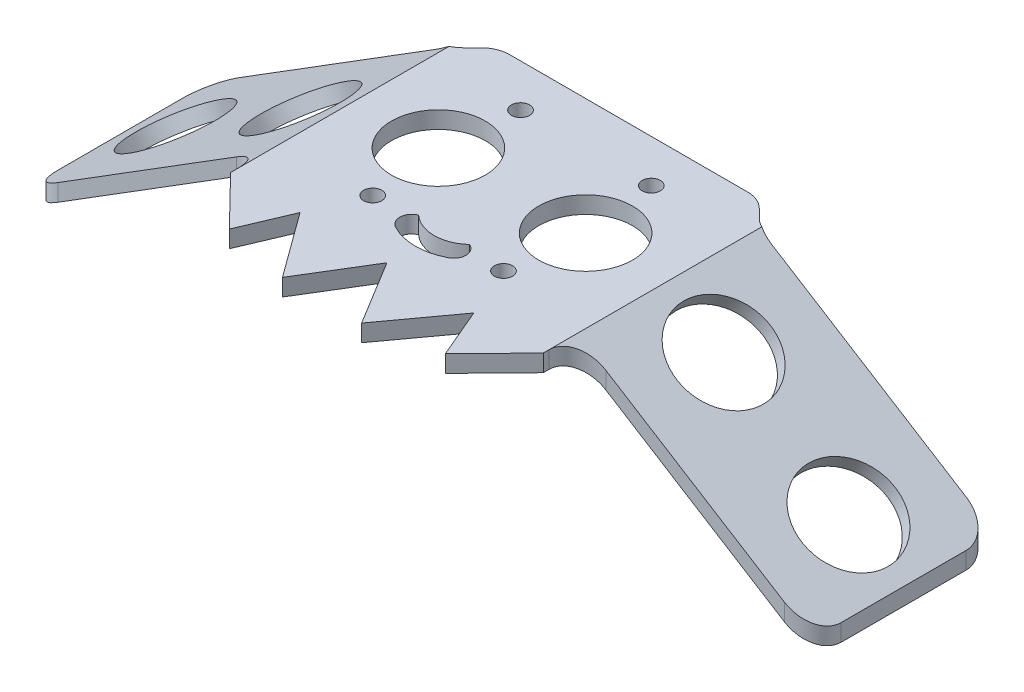
SolidWorks part; units mm, degrees
ref_plane "前视基准面" through (0, 0, 0) normal (0, 0, 1) x (1, 0, 0)
ref_plane "上视基准面" through (0, 0, 0) normal (0, 1, 0) x (1, 0, 0)
ref_plane "右视基准面" through (0, 0, 0) normal (1, 0, 0) x (0, 0, -1)
sketch "草图1" plane through (0, 0, 0) normal (0, 0, 1) x (1, 0, 0)
  line L0 (0, 148.5) -> (0, -94.9538) construction
  line L1 (105, -148.5) -> (-105, -148.5) construction
  line L2 (105, -148.5) -> (105, 148.5) construction
  line L3 (105, 148.5) -> (-105, 148.5) construction
  line L4 (-105, -148.5) -> (-105, 148.5) construction
  line L5 (105, -148.5) -> (-105, 148.5) construction
  line L6 (105, 148.5) -> (-105, -148.5) construction
  line L7 (35.8892, 121.6645) -> (-35.8892, 121.6645)
  line L8 (-35.8892, 121.6645) -> (-66.9017, 102.292)
  line L9 (-75, 40.9339) -> (-75, 31.2613)
  line L10 (-66.9017, 102.292) -> (-66.9017, 52.8701)
  line L11 (75, 40.9339) -> (75, 31.2613)
  line L12 (66.9017, 102.292) -> (66.9017, 52.8701)
  line L13 (35.8892, 121.6645) -> (66.9017, 102.292)
  line L14 (-75, 31.2613) -> (75, 31.2613)
  line L15 (-60, -148.5) -> (-60, -91.8129)
  line L16 (-75, 23.94) -> (75, 23.94)
  line L17 (-75, 23.94) -> (-75, 10.5626)
  line L18 (-38.8455, -105.5906) -> (-66.4608, -113.7617)
  line L19 (-66.4608, -113.7617) -> (-70.1743, -102.7328)
  line L20 (75, 23.94) -> (75, 10.5626)
  line L21 (66.4608, -113.7617) -> (70.1743, -102.7328)
  line L22 (38.8455, -105.5906) -> (66.4608, -113.7617)
  line L23 (-105, 93.0519) -> (105, 93.0519)
  line L24 (-105, 63.0519) -> (105, 63.0519)
  line L25 (-105, -90.0629) -> (-70.5337, -90.0629)
  line L26 (-105, -60.0629) -> (-67.4027, -60.0629)
  line L27 (60, -148.5) -> (60, 148.5)
  line L28 (-60, -58.3129) -> (-45, -58.3129)
  line L29 (-60, -61.8129) -> (-45, -61.8129)
  line L30 (-36, -58.3129) -> (-21, -58.3129)
  line L31 (-36, -61.8129) -> (-21, -61.8129)
  line L32 (-60, -88.3129) -> (-45, -88.3129)
  line L33 (-60, -91.8129) -> (-45, -91.8129)
  line L34 (-36, -88.3129) -> (-21, -88.3129)
  line L35 (-36, -91.8129) -> (-21, -91.8129)
  line L36 (-60, -58.3129) -> (-60, 148.5)
  line L37 (-19.25, -90.0629) -> (105, -90.0629)
  line L38 (-19.25, -60.0629) -> (19.25, -60.0629)
  line L39 (-60, -88.3129) -> (-60, -61.8129)
  line L40 (21, -58.3129) -> (36, -58.3129)
  line L41 (45, -58.3129) -> (60, -58.3129)
  line L42 (60, -61.8129) -> (45, -61.8129)
  line L43 (36, -61.8129) -> (21, -61.8129)
  line L44 (21, -88.3129) -> (36, -88.3129)
  line L45 (21, -91.8129) -> (36, -91.8129)
  line L46 (45, -88.3129) -> (60, -88.3129)
  line L47 (45, -91.8129) -> (60, -91.8129)
  line L48 (37.75, -60.0629) -> (43.25, -60.0629)
  line L49 (58.25, -60.0629) -> (105, -60.0629)
  line L50 (-60, 94.8019) -> (-45, 94.8019)
  line L51 (-36, 94.8019) -> (-21, 94.8019)
  line L52 (-60, 91.3019) -> (-45, 91.3019)
  line L53 (-36, 91.3019) -> (-21, 91.3019)
  line L54 (-60, 64.8019) -> (-45, 64.8019)
  line L55 (-60, 61.3019) -> (-45, 61.3019)
  line L56 (-36, 64.8019) -> (-21, 64.8019)
  line L57 (-36, 61.3019) -> (-21, 61.3019)
  line L58 (21, 94.8019) -> (36, 94.8019)
  line L59 (21, 91.3019) -> (36, 91.3019)
  line L60 (45, 94.8019) -> (60, 94.8019)
  line L61 (45, 91.3019) -> (60, 91.3019)
  line L62 (21, 61.3019) -> (36, 61.3019)
  line L63 (21, 64.8019) -> (36, 64.8019)
  line L64 (45, 61.3019) -> (60, 61.3019)
  line L65 (45, 64.8019) -> (60, 64.8019)
  line L66 (-33.1709, -104.7687) -> (33.1709, -104.7687)
  line L67 (0, -104.7687) -> (0, -148.5) construction
  arc A0 (-75, 40.9339) -> (-66.9017, 52.8701) centre (-79.7474, 52.8701) ccw
  arc A1 (75, 40.9339) -> (66.9017, 52.8701) centre (79.7474, 52.8701) cw
  arc A3 (-60, -88.3129) -> (-60, -91.8129) centre (-60, -90.0629) ccw
  arc A4 (-60, -58.3129) -> (-60, -61.8129) centre (-60, -60.0629) ccw
  circle A5 centre (-60, 63.0519) radius 1.75
  circle A6 centre (-60, 93.0519) radius 1.75
  circle A7 centre (60, 93.0519) radius 1.75
  circle A8 centre (60, 63.0519) radius 1.75
  arc A9 (60, -91.8129) -> (60, -88.3129) centre (60, -90.0629) ccw
  arc A10 (60, -61.8129) -> (60, -58.3129) centre (60, -60.0629) ccw
  arc A11 (-36, -58.3129) -> (-36, -61.8129) centre (-36, -60.0629) ccw
  arc A12 (-36, -88.3129) -> (-36, -91.8129) centre (-36, -90.0629) ccw
  arc A13 (36, -61.8129) -> (36, -58.3129) centre (36, -60.0629) ccw
  arc A14 (36, -91.8129) -> (36, -88.3129) centre (36, -90.0629) ccw
  arc A15 (-45, -61.8129) -> (-45, -58.3129) centre (-45, -60.0629) ccw
  arc A16 (-21, -61.8129) -> (-21, -58.3129) centre (-21, -60.0629) ccw
  arc A17 (-45, -91.8129) -> (-45, -88.3129) centre (-45, -90.0629) ccw
  arc A18 (-21, -91.8129) -> (-21, -88.3129) centre (-21, -90.0629) ccw
  arc A19 (45, -58.3129) -> (45, -61.8129) centre (45, -60.0629) ccw
  arc A20 (21, -58.3129) -> (21, -61.8129) centre (21, -60.0629) ccw
  arc A21 (21, -88.3129) -> (21, -91.8129) centre (21, -90.0629) ccw
  arc A22 (45, -88.3129) -> (45, -91.8129) centre (45, -90.0629) ccw
  circle A23 centre (-36, 93.0519) radius 1.75
  circle A24 centre (-36, 63.0519) radius 1.75
  circle A25 centre (36, 93.0519) radius 1.75
  circle A26 centre (36, 63.0519) radius 1.75
  circle A27 centre (-45, 93.0519) radius 1.75
  circle A28 centre (-21, 93.0519) radius 1.75
  circle A29 centre (-45, 63.0519) radius 1.75
  circle A30 centre (-21, 63.0519) radius 1.75
  circle A31 centre (21, 93.0519) radius 1.75
  circle A32 centre (21, 63.0519) radius 1.75
  circle A33 centre (45, 93.0519) radius 1.75
  circle A34 centre (45, 63.0519) radius 1.75
  arc A35 (33.1709, -104.7687) -> (38.8455, -105.5906) centre (33.1709, -124.7687) cw
  arc A36 (-33.1709, -104.7687) -> (-38.8455, -105.5906) centre (-33.1709, -124.7687) ccw
  spline S0 degree 3 poles (-75, 10.5626) (-72.6959, 1.9073) (-70.3396, -13.3728) (-67.1028, -43.6255) (-66.7657, -72.9327) (-71.8903, -95.1489) (-70.1743, -102.7328) knots 0 0 0 0 0.235247 0.406294 0.801186 1 1 1 1
  spline S1 degree 3 poles (75, 10.5626) (72.6959, 1.9073) (70.3396, -13.3728) (67.1028, -43.6255) (66.7657, -72.9327) (71.8903, -95.1489) (70.1743, -102.7328) knots 0 0 0 0 0.235247 0.406294 0.801186 1 1 1 1
  point P0 (0, 0)
  point P27 (0, 121.6645)
  point P42 (0, -94.0966)
  dimension "D1" = 60
  dimension "D4" = 20
  dimension "D5" = 24
  dimension "D7" = 24
  dimension "D9" = 15
  dimension "D10" = 15
  dimension "D13" = 24
  dimension "D17" = 15
  dimension "D2" = 30
  dimension "D3" = 30
  dimension "D6" = 24
  dimension "D8" = 24
  dimension "D11" = 15
  dimension "D12" = 15
  dimension "D14" = 24
  dimension "D15" = 24
  dimension "D16" = 24
  dimension "D18" = 15
  dimension "D19" = 15
  dimension "D20" = 15
  dimension "D21" = 15
  dimension "D22" = 15
  dimension "D23" = 15
  dimension "D24" = 15
  dimension "D25" = 15
  dimension "D26" = 15
  dimension "D27" = 15
  dimension "D28" = 15
  dimension "D29" = 3.5
  dimension "D30" = 3.5
  dimension "D31" = 3.5
extrude "凸台-拉伸1" add sketch "草图1" along normal blind 3 contours A34 L24 A26 L62 A32 A30 L57 A24 A29 L55 L36 L14 L27 L64 | A5 L24 L10 A0 L9 L14 L36 | A6 L23 L10 L24 A5 L36 | A6 L36 L8 L10 L23 | A33 L60 L27 L13 L7 L8 L36 L50 A27 L23 A23 L51 A28 A31 L58 A25 | A34 L65 L27 L61 A33 L23 A25 L59 A31 A28 L53 A23 A27 L52 L36 L54 A29 L24 A24 L56 A30 A32 L63 A26 | A7 L23 L12 L13 L27 | A8 L24 L12 L23 A7 L27 | A8 L27 L14 L11 A1 L12 L24 | A22 L46 L27 L42 A19 A13 L43 A20 A16 L31 A11 L30 L40 L41 L16 L36 L28 A15 L29 L39 L32 A17 L33 L15 L18 L22 L47 A14 L45 A21 A18 L35 A12 L34 | L17 S0 L19 L18 L15 A3 L39 A4 L36 L16 | S1 L20 L16 L27 A10 L49 | S1 L49 A10 L27 A9 L37 | S1 L37 A9 L27 L22 L21 region at (0, 106.7597, 0) region at (63.3118, 98.9762, 0) region at (-63.3118, 98.9762, 0) region at (63.5153, 78.0519, 0) region at (-63.5153, 78.0519, 0) region at (65.7633, 44.067, 0) region at (0, 78.0519, 0) region at (-65.7633, 44.067, 0) region at (0, 46.6707, 0) region at (0, -40.0712, 0) region at (65.6849, -11.6712, 0) region at (-65.3451, -38.0027, 0) region at (64.4303, -76.0355, 0) region at (65.0264, -100.7629, 0)
sketch "草图7" plane through (0, 0, 0) normal (0, 0, -1) x (-1, 0, 0)
  line L0 (0, 121.6645) -> (0, -104.7687) construction
  line L1 (-35.8892, 121.6645) -> (35.8892, 121.6645) construction
  line L2 (33.1709, -104.7687) -> (-33.1709, -104.7687) construction
  line L3 (0, 41.2613) -> (-21, 41.2613) construction
  line L4 (0, 41.2613) -> (21, 41.2613) construction
  line L5 (0, 13.94) -> (-21, 13.94) construction
  line L6 (0, 13.94) -> (21, 13.94) construction
  line L7 (75, 23.94) -> (-75, 23.94) construction
  line L8 (75, 31.2613) -> (-75, 31.2613) construction
  circle A0 centre (-21, 41.2613) radius 2.25
  circle A1 centre (21, 41.2613) radius 2.25
  circle A2 centre (-21, 13.94) radius 2.25
  circle A3 centre (21, 13.94) radius 2.25
  dimension "D1" = 10
  dimension "D2" = 10
extrude "切除-拉伸2" cut sketch "草图7" against normal through all
sketch "草图8" plane through (0, 0, 3) normal (0, 0, 1) x (1, 0, 0)
  line L0 (0, 121.6645) -> (0, -1.9696) construction
  line L1 (35.8892, 121.6645) -> (-35.8892, 121.6645) construction
  line L2 (-33.1709, -104.7687) -> (33.1709, -104.7687) construction
  line L3 (-33.409, 20.409) -> (-12.6214, -0.3786)
  line L4 (31.818, -51.182) -> (-31.818, -51.182)
  line L5 (35, -48) -> (35, 15.6418)
  line L8 (-35, 18.818) -> (-12.6214, -3.5605) construction
  line L9 (-33.409, -52.773) -> (-12.5737, -31.9377)
  line L10 (-36.591, 17.227) -> (-15.8034, -3.5605)
  line L11 (33.4105, 20.4105) -> (12.573, -0.427)
  line L12 (15.803, -3.5609) -> (36.5881, 17.2241)
  line L13 (31.8195, 18.8195) -> (-31.818, 18.818)
  line L14 (-15.8038, -28.8038) -> (-36.591, -49.591)
  line L15 (12.5534, -31.9174) -> (33.409, -52.773)
  line L16 (34.9993, 18.8173) -> (12.6207, -3.5613) construction
  line L17 (0, -30.3951) -> (0, -104.7687) construction
  line L18 (-35, -48) -> (-35, 15.636)
  line L19 (-11.9624, -1.9696) -> (-14.2124, -1.9696) construction
  line L20 (15.8034, -28.8034) -> (36.591, -49.591)
  line L21 (14.2117, -30.3951) -> (11.9607, -30.3951) construction
  line L22 (14.2117, -30.3951) -> (14.2117, -28.1441) construction
  line L23 (14.2117, -1.9696) -> (11.9612, -1.9696) construction
  line L24 (-14.2124, -30.3951) -> (-14.2124, -28.1446) construction
  line L25 (14.2117, -30.3951) -> (12.62, -28.8034) construction
  line L26 (14.2117, -1.9696) -> (12.6204, -3.5609) construction
  line L27 (12.6207, -28.8027) -> (35, -51.182) construction
  line L28 (-12.6215, -3.5606) -> (-14.2124, -1.9696) construction
  line L29 (-14.2124, -4.2196) -> (-14.2124, -1.9696) construction
  line L30 (-12.6214, -28.8034) -> (-35, -51.182) construction
  line L31 (-12.6211, -28.8037) -> (-14.2124, -30.3951) construction
  line L32 (-11.9619, -30.3951) -> (-14.2124, -30.3951) construction
  line L33 (14.2117, -4.2201) -> (14.2117, -1.9696) construction
  line L34 (11.0312, -30.3951) -> (0, -30.3951) construction
  arc A0 (-33.409, 20.409) -> (-36.591, 17.227) centre (-35, 18.818) ccw
  arc A1 (36.5881, 17.2241) -> (33.4105, 20.4105) centre (34.9993, 18.8173) ccw
  arc A2 (-36.591, -49.591) -> (-33.409, -52.773) centre (-35, -51.182) ccw
  arc A3 (33.409, -52.773) -> (36.591, -49.591) centre (35, -51.182) ccw
  arc A4 (-15.8034, -3.5605) -> (-12.6214, -0.3786) centre (-14.2124, -1.9696) ccw
  arc A5 (12.6692, -0.3308) -> (15.803, -3.5609) centre (14.2117, -1.9696) ccw
  arc A6 (-12.6699, -32.0338) -> (-15.8038, -28.8038) centre (-14.2124, -30.3951) ccw
  arc A7 (15.8034, -28.8034) -> (12.6894, -32.0534) centre (14.2117, -30.3951) ccw
  circle A8 centre (-0.0004, -16.1823) radius 8
  point P6 (0, -16.182)
  point P13 (-0.0004, -16.1823)
extrude "切除-拉伸3" cut sketch "草图8" against normal through all contours L10 A4 L3 A0 | L11 A5 L12 A1 | L20 A7 L15 A3 | L9 A6 L14 A2 | A8 region at (-24.6062, 8.4242, 3) region at (24.6054, 8.4234, 3) region at (-24.6061, -40.7881, 3) region at (24.6056, -40.7877, 3) region at (-0.0004, -16.1823, 3)
sketch "草图9" plane through (0, 0, 3) normal (0, 0, 1) x (1, 0, 0)
  line L0 (-70.7828, -98.747) -> (70.7828, -98.747) construction
  line L1 (0, -98.747) -> (0, -104.7687) construction
  line L2 (55, -100.497) -> (20, -100.497)
  line L3 (-55, -96.997) -> (-20, -96.997)
  line L4 (-55, -100.497) -> (-20, -100.497)
  line L5 (-33.1709, -104.7687) -> (33.1709, -104.7687) construction
  line L6 (55, -96.997) -> (20, -96.997)
  arc A0 (-55, -96.997) -> (-55, -100.497) centre (-55, -98.747) ccw
  arc A1 (-20, -100.497) -> (-20, -96.997) centre (-20, -98.747) ccw
  arc A2 (20, -100.497) -> (20, -96.997) centre (20, -98.747) cw
  arc A3 (55, -96.997) -> (55, -100.497) centre (55, -98.747) cw
  spline S0 degree 3 poles (-75, 10.5626) (-72.6959, 1.9073) (-70.3396, -13.3728) (-67.1028, -43.6255) (-66.7657, -72.9327) (-71.8903, -95.1489) (-70.1743, -102.7328) knots 0 0 0 0 0.235247 0.406294 0.801186 1 1 1 1 construction
  spline S1 degree 3 poles (75, 10.5626) (72.6959, 1.9073) (70.3396, -13.3728) (67.1028, -43.6255) (66.7657, -72.9327) (71.8903, -95.1489) (70.1743, -102.7328) knots 0 0 0 0 0.235247 0.406294 0.801186 1 1 1 1 construction
  dimension "D1" = 35
  dimension "D2" = 20
extrude "切除-拉伸4" cut sketch "草图9" against normal blind 3
sketch "草图10" plane through (0, 0, 3) normal (0, 0, 1) x (1, 0, 0)
  line L0 (-21, -60.0629) -> (-21, -90.0629) construction
  line L1 (21, -60.0629) -> (21, -90.0629) construction
  line L2 (-21, -75.0629) -> (-17.5, -75.0629) construction
  line L4 (12.5, -80.0629) -> (-12.5, -80.0629)
  line L6 (12.5, -70.0629) -> (-12.5, -70.0629)
  line L11 (17.5, -75.0629) -> (21, -75.0629) construction
  arc A0 (-12.5, -70.0629) -> (-12.5, -80.0629) centre (-12.5, -75.0629) ccw
  arc A1 (12.5, -80.0629) -> (12.5, -70.0629) centre (12.5, -75.0629) ccw
  point P11 (0, -75.0629)
extrude "切除-拉伸5" cut sketch "草图10" against normal blind 3
sketch "草图11" plane through (0, 0, 3) normal (0, 0, 1) x (1, 0, 0)
  line L0 (-21, 93.0519) -> (-21, 63.0519) construction
  line L1 (21, 93.0519) -> (21, 63.0519) construction
  line L2 (-21, 78.0519) -> (-20, 78.0519) construction
  line L4 (15, 73.0519) -> (-15, 73.0519)
  line L6 (15, 83.0519) -> (-15, 83.0519)
  line L10 (20, 78.0519) -> (21, 78.0519) construction
  arc A0 (-15, 83.0519) -> (-15, 73.0519) centre (-15, 78.0519) ccw
  arc A1 (15, 73.0519) -> (15, 83.0519) centre (15, 78.0519) ccw
  point P10 (0, 78.0519)
  dimension "D1" = 30
extrude "切除-拉伸8" cut sketch "草图11" against normal blind 3
sketch "草图12" plane through (0, 0, 3) normal (0, 0, 1) x (1, 0, 0)
  line L0 (0, 121.6645) -> (0, 83.0519) construction
  line L1 (35.8892, 121.6645) -> (-35.8892, 121.6645) construction
  line L2 (15, 83.0519) -> (-15, 83.0519) construction
  circle A0 centre (0, 106.3718) radius 11 construction
  circle A1 centre (0, 106.3718) radius 8 construction
  circle A2 centre (0, 114.3718) radius 1.7
  circle A3 centre (0, 98.3718) radius 1.7
  circle A4 centre (8, 106.3718) radius 1.7
  circle A5 centre (-8, 106.3718) radius 1.7
extrude "切除-拉伸9" cut sketch "草图12" against normal blind 3
sketch "草图13" plane through (0, 0, 3) normal (0, 0, 1) x (1, 0, 0)
  line L0 (0, -104.7687) -> (0, -80.0629) construction
  line L1 (-33.1709, -104.7687) -> (33.1709, -104.7687) construction
  line L2 (-12.5, -80.0629) -> (12.5, -80.0629) construction
  circle A0 centre (0, -92.4158) radius 8 construction
  circle A1 centre (0, -84.4158) radius 1.7
  circle A2 centre (8, -92.4158) radius 1.7
  circle A3 centre (0, -100.4158) radius 1.7
  circle A4 centre (-8, -92.4158) radius 1.7
extrude "切除-拉伸11" cut sketch "草图13" against normal blind 3
sketch "草图14" plane through (0, 0, 3) normal (0, 0, 1) x (1, 0, 0)
  line L0 (0, 23.94) -> (0, -104.7687) construction
  line L1 (-55.4755, 8.9197) -> (-55.4755, -46.0803)
  line L2 (-58.9755, 8.9197) -> (-58.9755, -46.0803)
  line L3 (-75, 23.94) -> (75, 23.94) construction
  line L4 (-33.1709, -104.7687) -> (33.1709, -104.7687) construction
  line L5 (58.9755, 8.9197) -> (58.9755, -46.0803)
  line L6 (55.4755, 8.9197) -> (55.4755, -46.0803)
  arc A0 (-55.4755, 8.9197) -> (-58.9755, 8.9197) centre (-57.2255, 8.9197) ccw
  arc A1 (-58.9755, -46.0803) -> (-55.4755, -46.0803) centre (-57.2255, -46.0803) ccw
  arc A2 (58.9755, -46.0803) -> (55.4755, -46.0803) centre (57.2255, -46.0803) cw
  arc A3 (55.4755, 8.9197) -> (58.9755, 8.9197) centre (57.2255, 8.9197) cw
extrude "切除-拉伸12" cut sketch "草图14" against normal through all
fillet "圆角1" radius 2 2 edges at (75, 31.2613, 1.5) (-75, 31.2613, 1.5)
fillet "圆角2" radius 2 2 edges at (-75, 23.94, 1.5) (75, 23.94, 1.5)
sketch "草图15" plane through (0, 0, 0) normal (0, 0, -1) x (-1, 0, 0)
  line L0 (0, 121.6645) -> (0, 31.2613) construction
  line L1 (-35.8892, 121.6645) -> (35.8892, 121.6645) construction
  line L2 (73, 31.2613) -> (-73, 31.2613) construction
  line L3 (-27.5188, 121.6645) -> (-63.6963, 99.0657) construction
  line L4 (-35.8892, 121.6645) -> (-66.9017, 102.292) construction
  line L5 (-61.1842, 102.4035) -> (-34.7748, 118.9006)
  line L6 (-59.5948, 99.8591) -> (-33.1854, 116.3562)
  line L7 (27.5188, 121.6645) -> (63.6963, 99.0657) construction
  line L8 (59.5948, 99.8591) -> (33.1854, 116.3562)
  line L9 (61.1842, 102.4035) -> (34.7748, 118.9006)
  arc A0 (-61.1842, 102.4035) -> (-59.5948, 99.8591) centre (-60.3895, 101.1313) ccw
  arc A1 (-33.1854, 116.3562) -> (-34.7748, 118.9006) centre (-33.9801, 117.6284) ccw
  arc A2 (33.1854, 116.3562) -> (34.7748, 118.9006) centre (33.9801, 117.6284) cw
  arc A3 (61.1842, 102.4035) -> (59.5948, 99.8591) centre (60.3895, 101.1313) cw
extrude "切除-拉伸13" cut sketch "草图15" against normal through all
sketch "草图16" plane through (0, 0, 0) normal (0, 0, -1) x (-1, 0, 0)
  line L0 (0, 121.6645) -> (0, 31.2613) construction
  line L1 (-35.8892, 121.6645) -> (35.8892, 121.6645) construction
  line L2 (73, 31.2613) -> (-73, 31.2613) construction
  line L3 (-21, 41.2613) -> (-66.71, 41.2613) construction
  line L4 (-61.517, 42.7613) -> (-32.0563, 42.7613)
  line L5 (-61.517, 39.7613) -> (-32.0563, 39.7613)
  line L6 (21, 41.2613) -> (66.71, 41.2613) construction
  line L7 (61.517, 39.7613) -> (32.0563, 39.7613)
  line L8 (61.517, 42.7613) -> (32.0563, 42.7613)
  arc A0 (-61.517, 42.7613) -> (-61.517, 39.7613) centre (-61.517, 41.2613) ccw
  arc A1 (-32.0563, 39.7613) -> (-32.0563, 42.7613) centre (-32.0563, 41.2613) ccw
  arc A2 (32.0563, 39.7613) -> (32.0563, 42.7613) centre (32.0563, 41.2613) cw
  arc A3 (61.517, 42.7613) -> (61.517, 39.7613) centre (61.517, 41.2613) cw
extrude "切除-拉伸14" cut sketch "草图16" against normal through all
sketch "草图17" plane through (0, 0, 0) normal (0, 0, -1) x (-1, 0, 0)
  text T0 "Y" font "黑体" height in points 72
extrude "切除-拉伸15" cut sketch "草图17" against normal through all
sketch "草图18" plane through (0, 0, 0) normal (0, 0, -1) x (-1, 0, 0)
  text T0 "H" font "黑体" height in points 72
extrude "切除-拉伸16" cut sketch "草图18" against normal through all
sketch "草图19" plane through (0, 0, 3) normal (0, 0, 1) x (1, 0, 0)
  line L2 (34.7748, 118.9006) -> (61.1842, 102.4035) construction
  line L3 (59.5948, 99.8591) -> (33.1854, 116.3562) construction
  line L6 (42.8907, 113.8308) -> (53.0682, 107.4733)
  line L7 (51.4789, 104.9289) -> (41.3014, 111.2864)
  line L8 (53.5457, 105.4064) -> (40.8239, 113.3533) construction
  line L10 (50.4193, 103.2326) -> (40.2418, 109.5902)
  line L11 (47.1848, 109.3799) -> (58.1535, 126.9392) construction
  line L12 (55.242, 104.3468) -> (61.9502, 115.0858)
  line L13 (39.1276, 114.4129) -> (45.8359, 125.1519)
  line L14 (61.9502, 115.0858) -> (45.8359, 125.1519)
  line L15 (35.8892, 121.6645) -> (66.9017, 102.292) construction
  arc A8 (51.4789, 104.9289) -> (53.0682, 107.4733) centre (52.2735, 106.2011) ccw
  arc A9 (42.8907, 113.8308) -> (41.3014, 111.2864) centre (42.096, 112.5586) ccw
  arc A10 (50.4193, 103.2326) -> (55.242, 104.3468) centre (52.2735, 106.2011) ccw
  arc A11 (39.1276, 114.4129) -> (40.2418, 109.5902) centre (42.096, 112.5586) ccw
  point P16 (47.1848, 109.3799)
  dimension "D3" = 8.2274
  dimension "D1" = 6
  dimension "D2" = 6
extrude "凸台-拉伸2" add sketch "草图19" along normal blind 3
sketch "草图20" plane through (0, 0, 6) normal (0, 0, 1) x (1, 0, 0)
  line L0 (45.3305, 106.4114) -> (53.8931, 120.1188) construction
  line L1 (40.2418, 109.5902) -> (50.4193, 103.2326) construction
  line L2 (61.9502, 115.0858) -> (45.8359, 125.1519) construction
  line L3 (61.9502, 115.0858) -> (45.8359, 125.1519)
  line L4 (60.3609, 112.5414) -> (44.2465, 122.6075)
  line L5 (45.8359, 125.1519) -> (44.2465, 122.6075)
  line L6 (60.3609, 112.5414) -> (61.9502, 115.0858)
  dimension "D1" = 3
extrude "凸台-拉伸3" add sketch "草图20" along normal blind 15
mirror "镜向1" about plane through (0, 0, 0) normal (1, 0, 0) of bodies 127
sketch "草图21" plane through (0, 121.6645, 0) normal (0, 1, 0) x (1, 0, 0)
  line L1 (-66.9017, -3) -> (64.5469, -3)
  line L2 (-66.9017, -3) -> (-66.9017, -35.9294)
  line L3 (-66.9017, -35.9294) -> (64.5469, -35.9294)
  line L4 (64.5469, -3) -> (64.5469, -35.9294)
extrude "切除-拉伸17" cut sketch "草图21" against normal blind 65 and the other way blind 45
ref_plane "基准面1" through (0, 0, 13) normal (0, 0, 1) x (1, 0, 0)
sketch "草图22" plane through (0, 0, 13) normal (0, 0, 1) x (1, 0, 0)
  line L0 (-8, 106.3718) -> (8, 106.3718) construction
  line L1 (-10.583, 101.3718) -> (10.583, 101.3718)
  line L2 (0, 101.3718) -> (0, 116.0718) construction
  line L4 (-15, 127.1092) -> (15, 127.1092)
  line L6 (-15, 127.1092) -> (-15, 101.3718)
  line L7 (-15, 101.3718) -> (15, 101.3718)
  line L8 (15, 127.1092) -> (15, 101.3718)
  line L9 (35.8892, 121.6645) -> (-35.8892, 121.6645) construction
  line L10 (-15, 101.3718) -> (-13.6906, 103.4239) construction
  circle A0 centre (0, 114.3718) radius 1.7 construction
  circle A1 centre (8, 106.3718) radius 1.7 construction
  circle A2 centre (-8, 106.3718) radius 1.7 construction
  circle A3 centre (0, 114.3718) radius 1.7
  circle A4 centre (8, 106.3718) radius 1.7
  circle A5 centre (-8, 106.3718) radius 1.7
  circle A7 centre (0, 106.3718) radius 3
  point P21 (-1.0292, 123.2666)
  dimension "D1" = 5
  dimension "D2" = 5.4446
  dimension "D3" = 15
  dimension "D4" = 15
extrude "凸台-拉伸4" add sketch "草图22" along normal blind 3 separate body contours L8 L4 L6 L7 L1 A7 A5 A4 A3 region at (-12.7915, 101.7671, 13)
fillet "圆角3" radius 5 2 edges at (15, 101.3718, 14.5) (-15, 101.3718, 14.5)
sketch "草图23" plane through (0, 0, 16) normal (0, 0, 1) x (1, 0, 0)
  line L0 (15, 127.1092) -> (15, 106.3718) construction
  line L1 (-15, 127.1092) -> (15, 127.1092)
  line L2 (-15, 127.1092) -> (-15, 124.1092)
  line L3 (-15, 124.1092) -> (15, 124.1092)
  line L4 (15, 127.1092) -> (15, 124.1092)
extrude "凸台-拉伸5" add sketch "草图23" along normal blind 35
sketch "草图25" plane through (0, 124.1092, 0) normal (0, -1, 0) x (1, 0, 0)
  line L0 (0, 16) -> (0, 51) construction
  line L1 (-10, 16) -> (10, 16) construction
  line L2 (-15, 51) -> (15, 51) construction
  line L3 (-15, 51) -> (-15, 16) construction
  line L4 (8, 51) -> (-8, 51)
  line L5 (8, 51) -> (8, 16)
  line L6 (8, 16) -> (-8, 16)
  line L7 (-8, 51) -> (-8, 16)
  line L8 (8, 51) -> (-8, 16) construction
  line L9 (8, 16) -> (-8, 51) construction
  point P6 (0, 33.5)
  dimension "D1" = 7
extrude "切除-拉伸18" cut sketch "草图25" against normal blind 35
fillet "圆角4" radius 3 2 edges at (-8, 125.6092, 16) (8, 125.6092, 16)
ref_plane "基准面2" through (0, 137.1092, 0) normal (0, 1, 0) x (1, 0, 0)
sketch "草图26" plane through (0, 137.1092, 0) normal (0, 1, 0) x (1, 0, 0)
  line L0 (0, 0) -> (0, -105.0488) construction
  line L1 (-8, -51) -> (-15, -51) construction
  line L2 (27.5, -51) -> (-27.5, -51)
  line L3 (27.5, -51) -> (27.5, -19)
  line L4 (27.5, -19) -> (-27.5, -19)
  line L5 (-27.5, -51) -> (-27.5, -19)
  line L6 (27.5, -51) -> (-27.5, -19) construction
  line L7 (27.5, -19) -> (-27.5, -51) construction
  line L8 (-27.5, -35) -> (27.5, -35) construction
  line L9 (0, -48.1253) -> (-21.2, -48.1253) construction
  line L10 (-21.2, -48.1253) -> (-21.2, -19) construction
  circle A1 centre (-12.95, -35) radius 8.25
  circle A2 centre (12.95, -35) radius 8.25
  point P3 (0, -35)
  dimension "D1" = 16.5
extrude "凸台-拉伸6" add sketch "草图26" along normal blind 3 separate body
sketch "草图27" plane through (0, 140.1092, 0) normal (0, 1, 0) x (1, 0, 0)
  line L0 (-15, -51) -> (-15, -13) construction
  line L1 (-49.7217, -13) -> (49.7217, -13) construction
  line L2 (-15, -51) -> (-15, -13) construction
  line L3 (-8, -51) -> (-8, -19) construction
  line L4 (0, -51) -> (0, -19) construction
  line L5 (-27.5, -51) -> (27.5, -51) construction
  line L6 (27.5, -19) -> (-27.5, -19) construction
  line L7 (-8, -19) -> (-15, -19) construction
  line L8 (-11.5, -19) -> (-11.5, -51) construction
  line L9 (-12.95, -35) -> (12.95, -35) construction
  circle A0 centre (-11.5, -22) radius 1.6
  circle A1 centre (-11.5, -48) radius 1.6
  circle A2 centre (11.5, -48) radius 1.6
  circle A3 centre (11.5, -22) radius 1.6
  dimension "D1" = 3
extrude "切除-拉伸19" cut sketch "草图27" against normal through all
sketch "草图29" plane through (0, 0, 19) normal (0, 0, -1) x (-1, 0, 0)
  line L0 (35.8892, 121.6645) -> (66.9017, 102.292) construction
  line L1 (-35.8892, 121.6645) -> (-66.9017, 102.292) construction
  line L2 (35.8892, 121.6645) -> (66.9017, 102.292)
  line L3 (-35.8892, 121.6645) -> (-66.9017, 102.292)
  line L4 (-27.5, 140.1092) -> (-68.9017, 114.2469)
  line L5 (-27.5, 137.1092) -> (-68.9017, 111.2469)
  line L6 (20.9, 137.1092) -> (-20.9, 137.1092) construction
  line L7 (27.5, 140.1092) -> (68.9017, 114.2469)
  line L8 (27.5, 137.1092) -> (68.9017, 111.2469)
  line L9 (68.9017, 111.2469) -> (68.9017, 114.2469)
  line L10 (0, 140.1092) -> (0, -104.7687) construction
  line L11 (-27.5, 140.1092) -> (27.5, 140.1092) construction
  line L12 (33.1709, -104.7687) -> (-33.1709, -104.7687) construction
  line L13 (-68.9017, 111.2469) -> (-68.9017, 114.2469)
  line L14 (27.5, 137.1092) -> (27.5, 140.1092)
  line L15 (-27.5, 137.1092) -> (-27.5, 140.1092)
  line M11 (27.5, 137.1092) -> (27.5, 140.1092)
  line M13 (-27.5, 140.1092) -> (-27.5, 137.1092)
extrude "凸台-拉伸7" add sketch "草图29" against normal up to surface (32 mm away) contours L8 L9 L7 M11 | L13 L5 L4 M13 region at (48.2008, 125.678, 19) region at (-48.2008, 125.678, 19) up to face at (0, 138.6092, 51)
sketch "草图31" plane through (-70.6744, 113.1395, 0) normal (-0.5298, 0.8481, 0) x (0.8481, 0.5298, 0)
  line L0 (2.0902, -35) -> (50.9057, -35) construction
  line L1 (2.0902, -51) -> (2.0902, -19) construction
  line L2 (50.9057, -19) -> (50.9057, -51) construction
  line L3 (26.498, -19) -> (26.498, -51) construction
  line L4 (50.9057, -19) -> (2.0902, -19) construction
  line L5 (2.0902, -51) -> (50.9057, -51) construction
  circle A0 centre (13.548, -35) radius 8.25
  circle A1 centre (39.448, -35) radius 8.25
  dimension "D1" = 16.5
  dimension "D2" = 16.5
  dimension "D3" = 12.95
  dimension "D4" = 12.95
extrude "切除-拉伸20" cut sketch "草图31" against normal blind 3
sketch "草图32" plane through (0, 140.1092, 0) normal (0, 1, 0) x (1, 0, 0)
  line L0 (27.5, -19) -> (-27.5, -19) construction
  point P0 (0, -19)
mirror "镜向3" about plane through (0, 0, 0) normal (1, 0, 0) of "切除-拉伸20"
sketch "草图33" plane through (0, 140.1092, 0) normal (0, 1, 0) x (1, 0, 0)
  line L0 (0, -51) -> (0, 0) construction
  line L1 (-27.5, -51) -> (27.5, -51) construction
  line L2 (23, -14.5) -> (-23, -14.5)
  line L3 (27.5, -19) -> (-27.5, -19) construction
  line L4 (-23, -14.5) -> (-27.5, -19)
  line L5 (23, -14.5) -> (27.5, -19)
  line L6 (-27.5, -19) -> (27.5, -19)
  point P12 (0, -14.5)
  dimension "D1" = 4.5
extrude "凸台-拉伸8" add sketch "草图33" against normal up to surface (3 mm away) up to face at (-11.5, 137.1092, 23.6)
fillet "圆角5" radius 5 4 edges at (27.5, 138.6092, 19) (23, 138.6092, 14.5) (-23, 138.6092, 14.5) (-27.5, 138.6092, 19)
fillet "圆角6" radius 5 4 edges at (68.9017, 112.7469, 51) (68.9017, 112.7469, 19) (-68.9017, 112.7469, 51) (-68.9017, 112.7469, 19)
sketch "草图34" plane through (0, 140.1092, 0) normal (0, 1, 0) x (1, 0, 0)
  line L0 (0, 0) -> (0, -144.922) construction
  line L5 (27.5, -51) -> (27.5, -63) construction
  line L11 (-27.5, -57) -> (-18.9932, -65.7222)
  line L13 (-27.5, -51) -> (27.5, -51)
  line L14 (-27.5, -51) -> (-27.5, -57)
  line L16 (27.5, -51) -> (27.5, -57)
  line L17 (-18.9932, -65.7222) -> (-15.2908, -57)
  line L18 (-15.2908, -57) -> (-6.9612, -68.4118)
  line L19 (-6.9612, -68.4118) -> (0, -57)
  line L20 (6.9612, -68.4118) -> (0, -57)
  line L21 (15.2908, -57) -> (6.9612, -68.4118)
  line L22 (18.9932, -65.7222) -> (15.2908, -57)
  line L23 (27.5, -57) -> (18.9932, -65.7222)
extrude "凸台-拉伸10" add sketch "草图34" against normal up to surface (3 mm away) contours L19 L20 L21 L22 L23 L16 L13 L14 L11 L17 L18 up to face at (-11.5, 137.1092, 23.6)
sketch "草图35" plane through (0, 140.1092, 0) normal (0, 1, 0) x (1, 0, 0)
  line L0 (0, -14.5) -> (0, -32.5134) construction
  line L1 (20.9289, -14.5) -> (-20.9289, -14.5) construction
  line L2 (6.9612, -68.4118) -> (0, -57) construction
  line L3 (0, -48.7039) -> (0, -57) construction
  arc A0 (-4.4758, -50.9044) -> (4.4758, -50.9044) centre (0, -42.1087) ccw
  arc A1 (-4.4758, -46.9527) -> (4.4758, -46.9527) centre (0, -42.1087) ccw
  arc A2 (-4.4758, -50.9044) -> (-4.4758, -46.9527) centre (-3.6937, -48.9286) cw
  arc A3 (4.4758, -50.9044) -> (4.4758, -46.9527) centre (3.6937, -48.9286) ccw
extrude "切除-拉伸21" cut sketch "草图35" against normal blind 5
fillet "圆角7" radius 5 2 edges at (27.5, 138.6092, 51) (-27.5, 138.6092, 51)
fillet "圆角8" radius 2 2 edges at (-10, 124.1092, 16) (10, 124.1092, 16)
fillet "圆角9" radius 2 4 edges at (-15, 125.6092, 51) (-8, 125.6092, 51) (8, 125.6092, 51) (15, 125.6092, 51)
fillet "圆角10" radius 2 1 edges at (0, 127.1092, 13)
sketch "草图36" plane through (0, 121.6645, 0) normal (0, 1, 0) x (1, 0, 0)
  line L1 (-80.2063, 5.0081) -> (79.8299, 5.0081)
  line L2 (-80.2063, 5.0081) -> (-80.2063, -8.5767)
  line L3 (-80.2063, -8.5767) -> (79.8299, -8.5767)
  line L4 (79.8299, 5.0081) -> (79.8299, -8.5767)
extrude "切除-拉伸22" cut sketch "草图36" against normal through all
sketch "草图37" plane through (0, 0, 13) normal (0, 0, -1) x (-1, 0, 0)
  line L1 (20.6073, 97.9332) -> (-26.1807, 97.9332)
  line L2 (20.6073, 97.9332) -> (20.6073, 132.2541)
  line L3 (20.6073, 132.2541) -> (-26.1807, 132.2541)
  line L4 (-26.1807, 97.9332) -> (-26.1807, 132.2541)
extrude "切除-拉伸23" cut sketch "草图37" against normal through all
